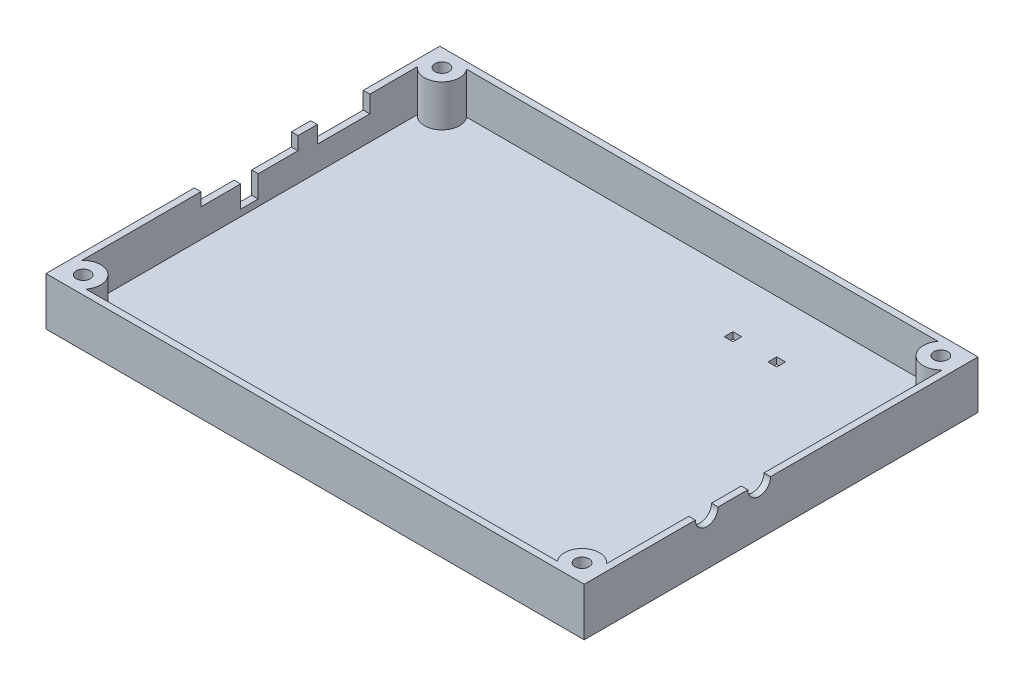
SolidWorks part; units mm, degrees
material "7079 Сплав"
ref_plane "Спереди" through (0, 0, 0) normal (0, 0, 1) x (1, 0, 0)
ref_plane "Сверху" through (0, 0, 0) normal (0, 1, 0) x (1, 0, 0)
ref_plane "Справа" through (0, 0, 0) normal (1, 0, 0) x (0, 0, -1)
sketch "Эскиз1" plane through (0, 0, 0) normal (0, 1, 0) x (1, 0, 0)
  line L1 (-61.5, 45) -> (61.5, 45)
  line L2 (-61.5, 45) -> (-61.5, -45)
  line L3 (-61.5, -45) -> (61.5, -45)
  line L4 (61.5, 45) -> (61.5, -45)
extrude "Бобышка-Вытянуть1" add sketch "Эскиз1" along normal blind 11
sketch "Эскиз2" plane through (0, 11, 0) normal (0, 1, 0) x (1, 0, 0)
  line L1 (60, -43.5) -> (-60, -43.5)
  line L2 (60, -43.5) -> (60, 43.5)
  line L3 (60, 43.5) -> (-60, 43.5)
  line L4 (-60, -43.5) -> (-60, 43.5)
  line L5 (60, -43.5) -> (-60, 43.5) construction
  line L6 (60, 43.5) -> (-60, -43.5) construction
  point P0 (0, 0)
extrude "Вырез-Вытянуть1" cut sketch "Эскиз2" against normal offset from surface (9.5 mm away) 1.5 up to face at (0, 0, 0)
sketch "Эскиз4" plane through (0, 1.5, 0) normal (0, 1, 0) x (1, 0, 0)
  circle A0 centre (-57, 41) radius 4
  circle A1 centre (57, 41) radius 4
  circle A2 centre (57, -41) radius 4
  circle A3 centre (-57, -41) radius 4
extrude "Бобышка-Вытянуть3" add sketch "Эскиз4" along normal up to surface (9.5 mm away) up to face at (0, 11, 0)
sketch "Эскиз5" plane through (0, 11, 0) normal (0, 1, 0) x (1, 0, 0)
  circle A0 centre (-57, 41) radius 1.6
  circle A1 centre (57, 41) radius 1.6
  circle A2 centre (57, -41) radius 1.6
  circle A3 centre (-57, -41) radius 1.6
extrude "Вырез-Вытянуть6" cut sketch "Эскиз5" against normal offset from surface (9.5 mm away) 1.5 up to face at (0, 0, 0)
sketch "Эскиз6" plane through (61.5, 0, 0) normal (1, 0, 0) x (0, 0, -1)
  circle A0 centre (-17, 11) radius 2.6
  circle A1 centre (-5, 11) radius 2.6
extrude "Вырез-Вытянуть7" cut sketch "Эскиз6" against normal up to surface (1.5 mm away) up to face at (60, 6.25, 0)
sketch "Эскиз7" plane through (-61.5, 0, 0) normal (-1, 0, 0) x (0, 0, 1)
  line L0 (-11.1, 8) -> (-2, 8)
  line L1 (2, 8) -> (11.1, 8)
  line L2 (-11.1, 8) -> (-11.1, 11)
  line L3 (-11.1, 11) -> (11.1, 11)
  line L4 (11.1, 8) -> (11.1, 11)
  line L5 (-15.5, 7.1) -> (-27.5, 7.1)
  line L6 (-15.5, 7.1) -> (-15.5, 11)
  line L7 (-15.5, 11) -> (-27.5, 11)
  line L8 (-27.5, 7.1) -> (-27.5, 11)
  line L9 (-2, 3) -> (2, 3)
  line L10 (-2, 3) -> (-2, 8)
  line L12 (2, 3) -> (2, 8)
extrude "Вырез-Вытянуть8" cut sketch "Эскиз7" against normal up to surface (1.5 mm away) up to face at (-60, 6.25, 0)
sketch "Эскиз8" plane through (0, 0, 0) normal (0, -1, 0) x (1, 0, 0)
  line L0 (29, -29.5) -> (31, -29.5)
  line L1 (19, -29.5) -> (21, -29.5)
  line L2 (19, -29.5) -> (19, -31.5)
  line L3 (19, -31.5) -> (21, -31.5)
  line L4 (21, -29.5) -> (21, -31.5)
  line L5 (19, -29.5) -> (21, -31.5) construction
  line L6 (19, -31.5) -> (21, -29.5) construction
  line L8 (29, -29.5) -> (29, -31.5)
  line L9 (29, -31.5) -> (31, -31.5)
  line L10 (31, -29.5) -> (31, -31.5)
  line L11 (29, -29.5) -> (31, -31.5) construction
  line L12 (29, -31.5) -> (31, -29.5) construction
  point P0 (20, -30.5)
  point P5 (30, -30.5)
extrude "Вырез-Вытянуть9" cut sketch "Эскиз8" against normal up to surface (1.5 mm away) up to face at (0, 1.5, 0)
sketch "Эскиз13" plane through (0, 0, 0) normal (0, -1, 0) x (1, 0, 0)
  line L0 (15, -27) -> (25, -27) construction
  line L1 (25, -27) -> (35, -27) construction
  line L2 (-50, 0) -> (50, 0) construction
  text T0 "Power" font "Arial" height in points 6
  text T1 "Network" font "Arial" height in points 6
  text T2 "GPS GSM Tracker" font "Arial Narrow" height in points 26
  point P5 (20, -27)
  point P8 (30, -27)
  point P11 (0, 0)
wrap "Переносить слова2" sketch "Эскиз13" wrap type scribe source sketch "Эскиз13" face at (30, 0, -30.5)
